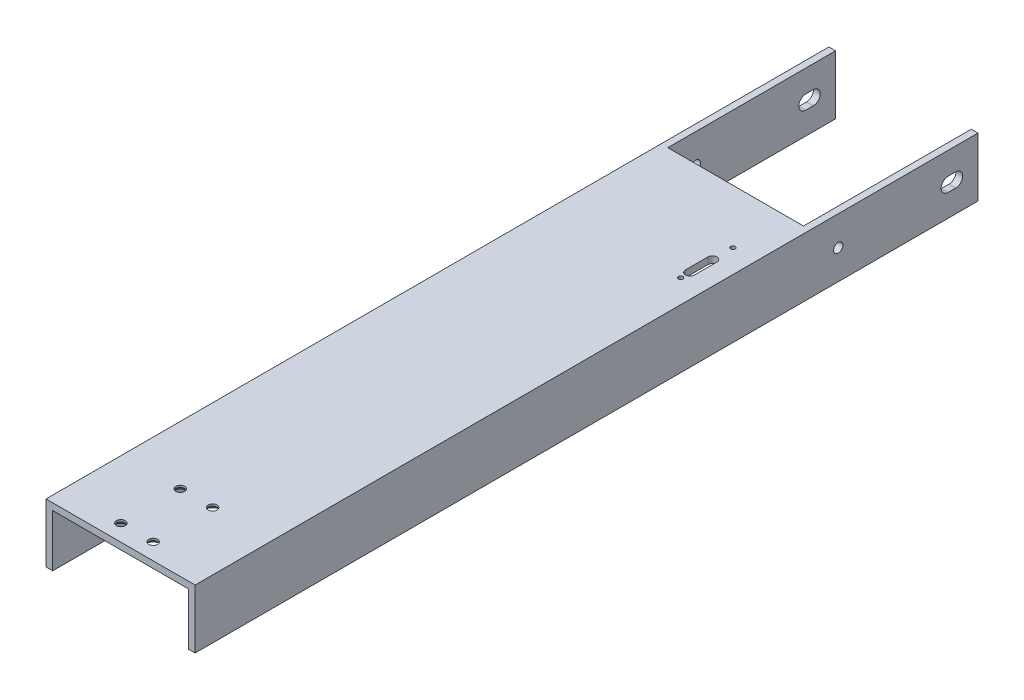
SolidWorks part; units mm, degrees
ref_plane "Front Plane" through (0, 0, 0) normal (0, 0, 1) x (1, 0, 0)
ref_plane "Top Plane" through (0, 0, 0) normal (0, 1, 0) x (1, 0, 0)
ref_plane "Right Plane" through (0, 0, 0) normal (1, 0, 0) x (0, 0, -1)
sketch "Sketch1" plane through (0, 0, 0) normal (0, 0, 1) x (1, 0, 0)
  line L0 (-50.8, 0) -> (50.8, 0)
  line L1 (50.8, 0) -> (50.8, -40.132)
  line L2 (50.8, -40.132) -> (46.228, -40.132)
  line L3 (46.228, -40.132) -> (46.228, -4.572)
  line L4 (46.228, -4.572) -> (-46.228, -4.572)
  line L5 (-46.228, -4.572) -> (-46.228, -40.132)
  line L6 (-46.228, -40.132) -> (-50.8, -40.132)
  line L7 (-50.8, -40.132) -> (-50.8, 0)
  point P8 (0, 0)
  dimension "D1" = 40.132
  dimension "D2" = 4.572
  dimension "D3" = 4.572
  dimension "D4" = 101.6
extrude "Boss-Extrude1" add sketch "Sketch1" along normal blind 533.4
sketch "Sketch3" plane through (0, 0, 0) normal (0, 1, 0) x (1, 0, 0)
  line L0 (50.8, 0) -> (-50.8, 0) construction
  line L1 (-46.228, -114.3) -> (46.228, -114.3)
  line L2 (-46.228, -114.3) -> (-46.228, 0)
  line L3 (-46.228, 0) -> (46.228, 0)
  line L4 (46.228, -114.3) -> (46.228, 0)
  line L5 (-46.228, -114.3) -> (46.228, 0) construction
  line L6 (-46.228, 0) -> (46.228, -114.3) construction
  line L7 (-46.228, -533.4) -> (-46.228, 0) construction
  line L8 (46.228, -533.4) -> (46.228, 0) construction
  line L9 (34.925, -165.1) -> (34.925, -180.34) construction
  line L10 (37.973, -165.1) -> (37.973, -180.34)
  line L11 (31.877, -165.1) -> (31.877, -180.34)
  line L12 (0, -1000) -> (0, 49000) construction
  line L13 (50.8, -533.4) -> (-50.8, -533.4) construction
  arc A0 (37.973, -165.1) -> (31.877, -165.1) centre (34.925, -165.1) ccw
  arc A1 (31.877, -180.34) -> (37.973, -180.34) centre (34.925, -180.34) ccw
  circle A2 centre (34.925, -151.13) radius 1.524
  circle A3 centre (34.925, -186.69) radius 1.524
  circle A4 centre (-11.0109, -522.1859) radius 3
  circle A5 centre (11.0109, -481.6729) radius 3
  circle A6 centre (-11.0109, -481.6729) radius 3
  circle A7 centre (11.0109, -522.1859) radius 3
  point P0 (0, -57.15)
  point P13 (34.925, -172.72)
  dimension "D2" = 6.096
  dimension "D6" = 3.048
  dimension "D9" = 6
  dimension "D1" = 114.3
  dimension "D3" = 15.24
  dimension "D4" = 50.8
  dimension "D5" = 8.255
  dimension "D7" = 13.97
  dimension "D8" = 6.35
  dimension "D10" = 40.513
  dimension "D11" = 22.0218
  dimension "D12" = 11.2141
extrude "Cut-Extrude1" cut sketch "Sketch3" against normal through all
sketch "Sketch4" plane through (50.8, 0, 0) normal (1, 0, 0) x (0, 0, -1)
  line L0 (-15.24, -20.066) -> (-20.32, -20.066) construction
  line L1 (-15.24, -24.8285) -> (-20.32, -24.8285)
  line L2 (-15.24, -15.3035) -> (-20.32, -15.3035)
  line L3 (0, -40.132) -> (0, 0) construction
  arc A0 (-15.24, -24.8285) -> (-15.24, -15.3035) centre (-15.24, -20.066) ccw
  arc A1 (-20.32, -15.3035) -> (-20.32, -24.8285) centre (-20.32, -20.066) ccw
  circle A2 centre (-95.25, -20.066) radius 3.175
  point P3 (-17.78, -20.066)
  point P10 (0, -20.066)
  dimension "D3" = 9.525
  dimension "D5" = 6.35
  dimension "D1" = 5.08
  dimension "D2" = 15.24
  dimension "D4" = 95.25
extrude "Cut-Extrude2" cut sketch "Sketch4" against normal through all
chamfer "Chamfer1" distance 3.25 angle 45 4 edges at (8.0109, -4.572, 481.6729) (8.0109, -4.572, 522.1859) (-14.0109, -4.572, 522.1859) (-14.0109, -4.572, 481.6729)
